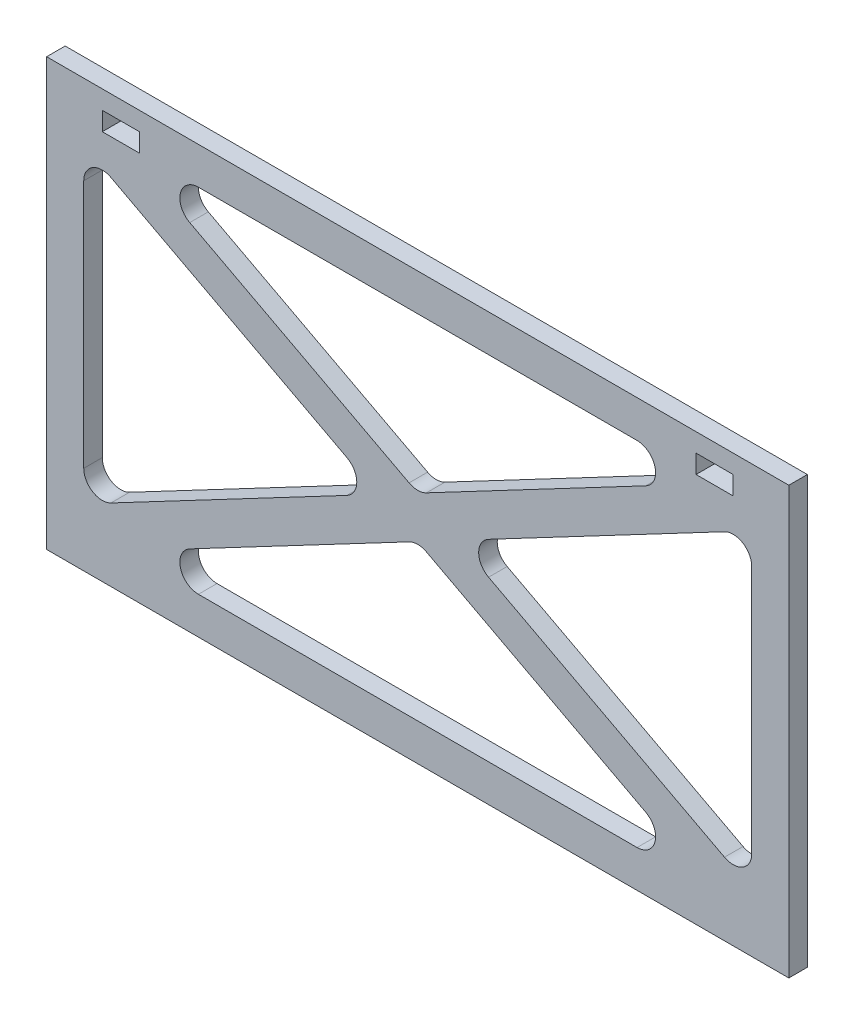
SolidWorks part; units mm, degrees
material "Beech"
ref_plane "Front Plane" through (0, 0, 0) normal (0, 0, 1) x (1, 0, 0)
ref_plane "Top Plane" through (0, 0, 0) normal (0, 1, 0) x (1, 0, 0)
ref_plane "Right Plane" through (0, 0, 0) normal (1, 0, 0) x (0, 0, -1)
sketch "Sketch1" plane through (0, 0, 0) normal (0, 0, 1) x (1, 0, 0)
  line L0 (91.44, 48.26) -> (-91.44, 48.26)
  line L1 (101.6, 58.42) -> (-101.6, 58.42)
  line L2 (101.6, 58.42) -> (101.6, -58.42)
  line L3 (101.6, -58.42) -> (-101.6, -58.42)
  line L4 (-101.6, 58.42) -> (-101.6, -58.42)
  line L5 (101.6, 58.42) -> (-101.6, -58.42) construction
  line L6 (101.6, -58.42) -> (-101.6, 58.42) construction
  line L7 (-91.44, 48.26) -> (-91.44, -48.26)
  line L8 (91.44, -48.26) -> (-91.44, -48.26)
  line L9 (91.44, 48.26) -> (91.44, -48.26)
  line L10 (-91.44, 48.26) -> (91.44, -48.26) construction
  line L11 (-91.44, -48.26) -> (91.44, 48.26) construction
  line L12 (-93.8111, 43.7673) -> (89.0689, -52.7527)
  line L13 (-89.0689, -52.7527) -> (93.8111, 43.7673)
  line L14 (-89.0689, 52.7527) -> (93.8111, -43.7673)
  line L15 (-93.8111, -43.7673) -> (89.0689, 52.7527)
  line L16 (0, 0) -> (0, 58.42) construction
  point P0 (0, 0)
  dimension "D1" = 116.84
  dimension "D2" = 203.2
  dimension "D3" = 10.16
  dimension "D4" = 5.08
  dimension "D5" = 5.08
extrude "Boss-Extrude1" add sketch "Sketch1" along normal blind 5.08 contours L1 L4 L3 L2 L0 L9 L8 L7 | L12 L15 L14 L0 L7 | L15 L14 L13 L9 L0 | L15 L12 L13 L14 | L15 L7 L8 L13 L12 | L14 L13 L12 L8 L9 | L14 L0 | L15 L0 region at (47.0953, 24.8558, 0) region at (-47.0953, 24.8558, 0) region at (0, 0, 0) region at (47.0953, -24.8558, 0) region at (-47.0953, -24.8558, 0) region at (99.256, 0, 0)
fillet "Fillet1" radius 5.08 12 edges at (10.8836, 0, 2.54) (91.44, -42.5159, 2.54) (80.5564, -48.26, 2.54) (-80.5564, -48.26, 2.54) (91.44, 42.5159, 2.54) (80.5564, 48.26, 2.54) (-80.5564, 48.26, 2.54) (0, -5.7441, 2.54) (-10.8836, 0, 2.54) (0, 5.7441, 2.54) (-91.44, -42.5159, 2.54) (-91.44, 42.5159, 2.54)
sketch "Sketch2" plane through (0, 0, 5.08) normal (0, 0, 1) x (1, 0, 0)
  line L0 (-86.36, 53.34) -> (-76.2, 53.34)
  line L1 (-86.36, 53.34) -> (-86.36, 48.26)
  line L2 (-86.36, 48.26) -> (-76.2, 48.26)
  line L3 (-76.2, 53.34) -> (-76.2, 48.26)
  line L4 (-86.36, 53.34) -> (-76.2, 48.26) construction
  line L5 (-86.36, 48.26) -> (-76.2, 53.34) construction
  line L6 (-101.6, 58.42) -> (-101.6, -58.42) construction
  line L7 (101.6, 58.42) -> (-101.6, 58.42) construction
  line L8 (0, 0) -> (0, 58.42) construction
  line L9 (86.36, 48.26) -> (76.2, 53.34) construction
  line L10 (86.36, 53.34) -> (76.2, 48.26) construction
  line L11 (76.2, 53.34) -> (76.2, 48.26)
  line L12 (86.36, 48.26) -> (76.2, 48.26)
  line L13 (86.36, 53.34) -> (86.36, 48.26)
  line L14 (86.36, 53.34) -> (76.2, 53.34)
  point P4 (-81.28, 50.8)
  point P16 (81.28, 50.8)
  dimension "D1" = 20.32
  dimension "D2" = 7.62
  dimension "D3" = 10.16
  dimension "D4" = 5.08
extrude "Cut-Extrude1" cut sketch "Sketch2" against normal through all both and the other way through all
